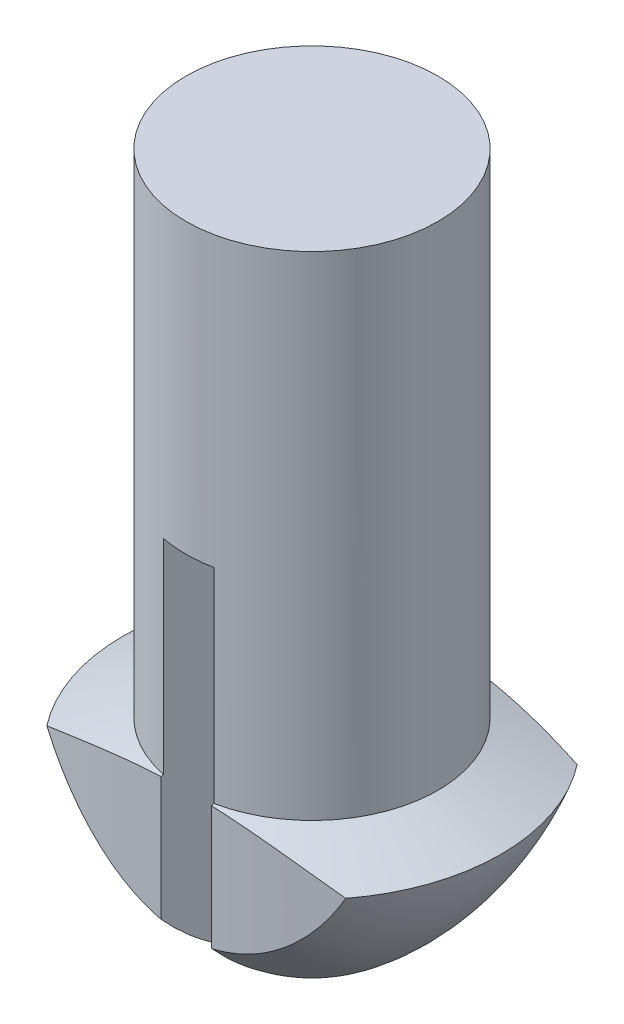
SolidWorks part; units mm, degrees
ref_plane "Front Plane" through (0, 0, 0) normal (0, 0, 1) x (1, 0, 0)
ref_plane "Top Plane" through (0, 0, 0) normal (0, 1, 0) x (1, 0, 0)
ref_plane "Right Plane" through (0, 0, 0) normal (1, 0, 0) x (0, 0, -1)
sketch "Sketch1" plane through (0, 0, 0) normal (0, 0, 1) x (1, 0, 0)
  line L0 (11.7423, -25.5723) -> (11.7423, -27.0723)
  line L1 (11.7423, -21.4723) -> (12.7423, -21.4723)
  line L2 (11.7423, -21.4723) -> (11.7423, -25.5723)
  line L3 (13.2423, -25.5723) -> (12.7423, -25.3828)
  line L4 (12.7423, -21.4723) -> (12.7423, -25.3828)
  arc A0 (11.7423, -27.0723) -> (13.2423, -25.5723) centre (10.8267, -24.6567) ccw
  dimension "D1" = 1
  dimension "D2" = 1.5
  dimension "D4" = 1.5
revolve "Revolve1" add sketch "Sketch1" angle 360 about L2
sketch "Sketch2" plane through (0, 0, 0) normal (0, 0, 1) x (1, 0, 0)
  line L0 (11.5423, -27.0723) -> (11.5423, -23.76)
  line L1 (11.5423, -27.0723) -> (11.9423, -27.0723)
  line L3 (11.5423, -23.76) -> (11.9423, -23.76)
  line L4 (11.9423, -27.0723) -> (11.9423, -23.76)
  dimension "D1" = 0.4
extrude "Cut-Extrude1" cut sketch "Sketch2" against normal blind 25.4 and the other way blind 25.4
sketch "Sketch3" plane through (0, 0, 0) normal (0, 1, 0) x (1, 0, 0)
  ellipse E0 centre (11.7423, 0) end of major axis (14.7423, 0) minor radius 1
  ellipse E1 centre (11.7423, 0) end of major axis (37.1423, 0) minor radius 25.4
extrude "Cut-Extrude2" cut sketch "Sketch3" against normal blind 50.8
